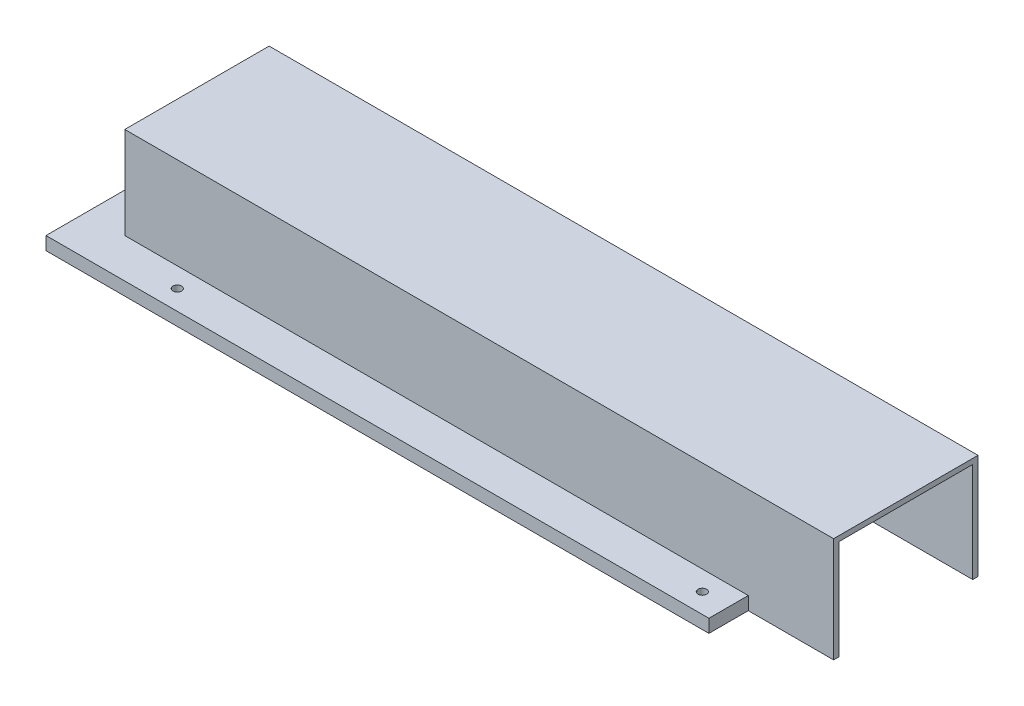
SolidWorks part; units mm, degrees
ref_plane "Front Plane" through (0, 0, 0) normal (0, 0, 1) x (1, 0, 0)
ref_plane "Top Plane" through (0, 0, 0) normal (0, 1, 0) x (1, 0, 0)
ref_plane "Right Plane" through (0, 0, 0) normal (1, 0, 0) x (0, 0, -1)
sketch "Sketch1" plane through (0, 0, 0) normal (0, 1, 0) x (1, 0, 0)
  line L1 (-125.5, -25.5) -> (125.5, -25.5)
  line L2 (-125.5, -25.5) -> (-125.5, 25.5)
  line L3 (-125.5, 25.5) -> (125.5, 25.5)
  line L4 (125.5, -25.5) -> (125.5, 25.5)
  line L5 (-125.5, -25.5) -> (125.5, 25.5) construction
  line L6 (-125.5, 25.5) -> (125.5, -25.5) construction
  line L7 (-142.5, -42.5) -> (142.5, -42.5)
  line L8 (-142.5, -42.5) -> (-142.5, 42.5)
  line L9 (-142.5, 42.5) -> (142.5, 42.5)
  line L10 (142.5, -42.5) -> (142.5, 42.5)
  line L11 (-142.5, -42.5) -> (142.5, 42.5) construction
  line L12 (-142.5, 42.5) -> (142.5, -42.5) construction
  point P0 (0, 0)
  point P6 (0, 0)
  dimension "D1" = 251
  dimension "D2" = 51
  dimension "D3" = 17
  dimension "D4" = 17
extrude "Boss-Extrude1" add sketch "Sketch1" along normal blind 5
sketch "Sketch2" plane through (0, 5, 0) normal (0, 1, 0) x (1, 0, 0)
  line L0 (125.5, -25.5) -> (125.5, 25.5) construction
  line L1 (-125.5, -25.5) -> (125.5, -25.5) construction
  line L2 (-125.5, 25.5) -> (-125.5, -25.5) construction
  line L3 (125.5, 25.5) -> (-125.5, 25.5) construction
  line L4 (125.5, -25.5) -> (125.5, 25.5)
  line L5 (-125.5, -25.5) -> (125.5, -25.5)
  line L6 (-125.5, 25.5) -> (-125.5, -25.5)
  line L7 (125.5, 25.5) -> (-125.5, 25.5)
  line L8 (127.5, 27.5) -> (-127.5, 27.5)
  line L9 (-127.5, 27.5) -> (-127.5, -27.5)
  line L10 (-127.5, -27.5) -> (127.5, -27.5)
  line L11 (127.5, -27.5) -> (127.5, 27.5)
  line L12 (127.5, 27.5) -> (142.5, 27.5)
  line L13 (142.5, -42.5) -> (142.5, 42.5) construction
  line L14 (127.5, -27.5) -> (142.5, -27.5)
  line L15 (142.5, -27.5) -> (142.5, 27.5)
  line L16 (127.5, 27.5) -> (127.5, -27.5)
  line M9 (142.5, -42.5) -> (142.5, 42.5)
  line M13 (125.5, 25.5) -> (125.5, -25.5)
  line M14 (125.5, -25.5) -> (-125.5, -25.5)
  line M15 (-125.5, -25.5) -> (-125.5, 25.5)
  line M16 (-125.5, 25.5) -> (125.5, 25.5)
  dimension "D1" = 2
extrude "Boss-Extrude2" add sketch "Sketch2" along normal blind 35 contours L11 L14 L12 M9 | L10 L11 L8 L9 M16 M13 M14 M15 region at (127.2391, 5, 0) region at (135, 5, 0)
sketch "Sketch3" plane through (0, 40, 0) normal (0, 1, 0) x (1, 0, 0)
  line L4 (142.5, 27.5) -> (-127.5, 27.5)
  line L5 (-127.5, 27.5) -> (-127.5, -27.5)
  line L6 (-127.5, -27.5) -> (142.5, -27.5)
  line L7 (142.5, -27.5) -> (142.5, 27.5)
  line L8 (142.5, 27.5) -> (-127.5, 27.5)
  line L9 (-127.5, 27.5) -> (-127.5, -27.5)
  line L10 (-127.5, -27.5) -> (142.5, -27.5)
  line L11 (142.5, -27.5) -> (142.5, 27.5)
  dimension "D1" = 0
extrude "Boss-Extrude3" add sketch "Sketch3" against normal blind 2
sketch "Sketch4" plane through (142.5, 0, 0) normal (1, 0, 0) x (0, 0, -1)
  line L0 (-42.5, 0) -> (42.5, 0) construction
  line L1 (-25.5, 0) -> (25.5, 0)
  line L2 (-25.5, 0) -> (-25.5, 38)
  line L3 (-25.5, 38) -> (25.5, 38)
  line L4 (25.5, 0) -> (25.5, 38)
  line L5 (-25.5, 0) -> (25.5, 38) construction
  line L6 (-25.5, 38) -> (25.5, 0) construction
  line L7 (-27.5, 40) -> (27.5, 40) construction
  line L8 (27.5, 40) -> (27.5, 5) construction
  point P0 (0, 19)
  point P5 (0, 0)
  point P7 (0, 0)
  dimension "D1" = 2
  dimension "D2" = 2
extrude "Cut-Extrude1" cut sketch "Sketch4" against normal blind 17
hole_wizard "M4x0.7 Tapped Hole1" positions "Sketch5" profile "Sketch7" tap size "M4x0.7" standard "ANSI Metric" end condition through all
sketch "Sketch5" plane through (0, 5, 0) normal (0, 1, 0) x (1, 0, 0)
  line L1 (-100, -35) -> (100, -35)
  line L2 (-100, -35) -> (-100, 35)
  line L3 (-100, 35) -> (100, 35)
  line L4 (100, -35) -> (100, 35)
  line L5 (-100, -35) -> (100, 35) construction
  line L6 (-100, 35) -> (100, -35) construction
  point P2 (100, 35)
  point P139 (-100, -35)
  point P140 (-100, 35)
  point P141 (100, -35)
  point P153 (0, 0)
  dimension "D1" = 70
  dimension "D2" = 200
sketch "Sketch7" plane through (100, 5, -35) normal (1, 0, 0) x (0, 0, 1)
  line L0 (0, 0) -> (0, 5)
  line L1 (0, 5) -> (1.65, 5)
  line L2 (1.65, 5) -> (1.65, 0)
  line L5 (1.65, 0) -> (0, 0)
  line L11 (0, -6.35) -> (0, 107.95) construction
  dimension "Thru Tap Drill Dia." = 3.3
  dimension "Thru Tap Drill Depth" = 5
cosmetic thread "Hole Thread1" parameters "D2"=4
cosmetic thread "Hole Thread2" parameters "D2"=4
cosmetic thread "Hole Thread3" parameters "D2"=4
cosmetic thread "Hole Thread4" parameters "D2"=4
sketch "Sketch8" plane through (0, 5, 0) normal (0, 1, 0) x (1, 0, 0)
  line L0 (110, 42.5) -> (110, -42.5)
  line L8 (-127.5, -27.5) -> (-127.5, 27.5)
  line L9 (-127.5, 27.5) -> (142.5, 27.5)
  line L10 (142.5, 27.5) -> (142.5, 42.5)
  line L11 (142.5, 42.5) -> (-142.5, 42.5)
  line L12 (-142.5, 42.5) -> (-142.5, -42.5)
  line L13 (-142.5, -42.5) -> (142.5, -42.5)
  line L14 (142.5, -42.5) -> (142.5, -27.5)
  line L15 (142.5, -27.5) -> (-127.5, -27.5)
  line L16 (-127.5, -27.5) -> (-127.5, 27.5)
  line L17 (-127.5, 27.5) -> (142.5, 27.5)
  line L18 (142.5, 27.5) -> (142.5, 42.5)
  line L19 (142.5, 42.5) -> (-142.5, 42.5)
  line L20 (-142.5, 42.5) -> (-142.5, -42.5)
  line L21 (-142.5, -42.5) -> (142.5, -42.5)
  line L22 (142.5, -42.5) -> (142.5, -27.5)
  line L23 (142.5, -27.5) -> (-127.5, -27.5)
  circle A0 centre (100, 35) radius 1.65 construction
  line M15 (-127.5, 27.5) -> (142.5, 27.5)
  line M16 (142.5, 27.5) -> (142.5, 42.5)
  line M17 (142.5, 42.5) -> (-142.5, 42.5)
  line M19 (-142.5, -42.5) -> (142.5, -42.5)
  line M20 (142.5, -42.5) -> (142.5, -27.5)
  line M21 (142.5, -27.5) -> (-127.5, -27.5)
  dimension "D2" = 10
  dimension "D1" = 0
extrude "Cut-Extrude2" cut sketch "Sketch8" against normal blind 10 contours L0 M17 M15 M16 | L0 M21 M19 M20 region at (126.25, 5, -35) region at (126.25, 5, 35)
